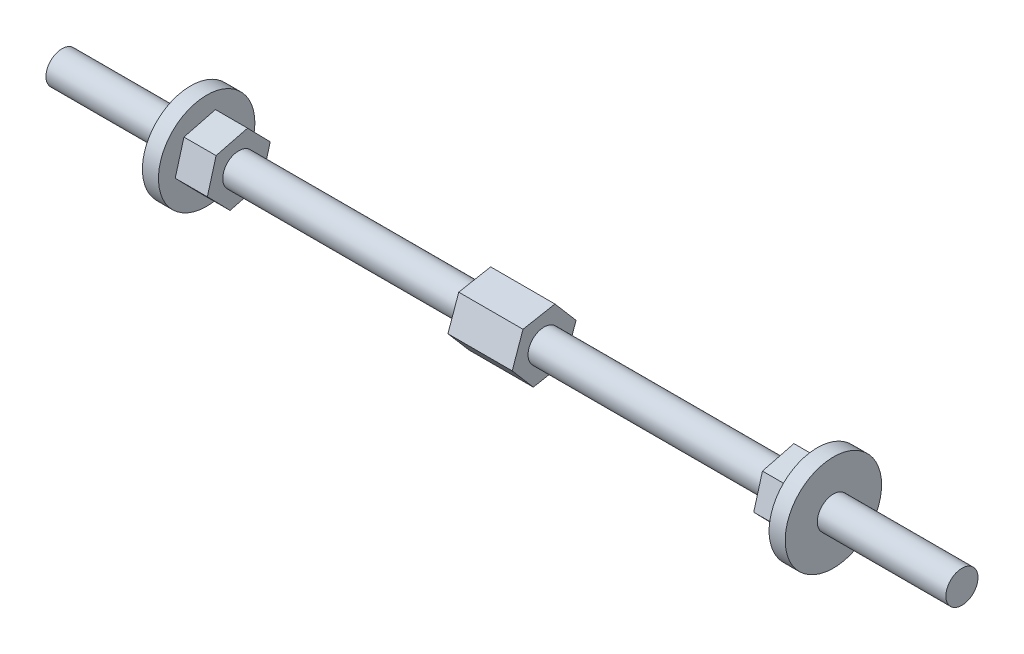
SolidWorks part; units mm, degrees
ref_plane "Front Plane" through (0, 0, 0) normal (0, 0, 1) x (1, 0, 0)
ref_plane "Top Plane" through (0, 0, 0) normal (0, 1, 0) x (1, 0, 0)
ref_plane "Right Plane" through (0, 0, 0) normal (1, 0, 0) x (0, 0, -1)
sketch "Sketch2" plane through (0, 0, 0) normal (1, 0, 0) x (0, 0, -1)
  line L1 (4.1712, -4.8748) -> (6.3073, 1.175)
  line L2 (6.3073, 1.175) -> (2.1361, 6.0498)
  line L3 (2.1361, 6.0498) -> (-4.1712, 4.8748)
  line L4 (-4.1712, 4.8748) -> (-6.3073, -1.175)
  line L5 (-6.3073, -1.175) -> (-2.1361, -6.0498)
  line L6 (-2.1361, -6.0498) -> (4.1712, -4.8748)
  circle A1 centre (0, 0) radius 5.5563 construction
  dimension "D2" = 5.5562
extrude "Boss-Extrude1" add sketch "Sketch2" along normal blind 6.35 and the other way blind 6.35
sketch "Sketch3" plane through (6.35, 0, 0) normal (1, 0, 0) x (0, 0, -1)
  circle A0 centre (0, 0) radius 3.175
  dimension "D1" = 6.35
extrude "Boss-Extrude2" add sketch "Sketch3" along normal blind 47.625 and the other way blind 60.325
sketch "Sketch4" plane through (53.975, 0, 0) normal (1, 0, 0) x (0, 0, -1)
  line L1 (4.4881, -4.5847) -> (6.2145, 1.5945)
  line L2 (6.2145, 1.5945) -> (1.7264, 6.1792)
  line L3 (1.7264, 6.1792) -> (-4.4881, 4.5847)
  line L4 (-4.4881, 4.5847) -> (-6.2145, -1.5945)
  line L5 (-6.2145, -1.5945) -> (-1.7264, -6.1792)
  line L6 (-1.7264, -6.1792) -> (4.4881, -4.5847)
  circle A0 centre (0, 0) radius 5.5563 construction
  dimension "D1" = 5.5562
extrude "Boss-Extrude3" add sketch "Sketch4" along normal blind 6.35
sketch "Sketch5" plane through (60.325, 0, 0) normal (1, 0, 0) x (0, 0, -1)
  circle A0 centre (0, 0) radius 9.525
  dimension "D1" = 19.05
extrude "Boss-Extrude4" add sketch "Sketch5" along normal blind 3.175
mirror "Mirror1" about plane through (0, 0, 0) normal (1, 0, 0) of "Boss-Extrude3", "Boss-Extrude4"
sketch "Sketch7" plane through (63.5, 0, 0) normal (1, 0, 0) x (0, 0, -1)
  circle A0 centre (0, 0) radius 3.175
  dimension "D1" = 6.35
extrude "Boss-Extrude5" add sketch "Sketch7" along normal blind 25.4
mirror "Mirror3" about plane through (0, 0, 0) normal (1, 0, 0) of "Boss-Extrude5"
